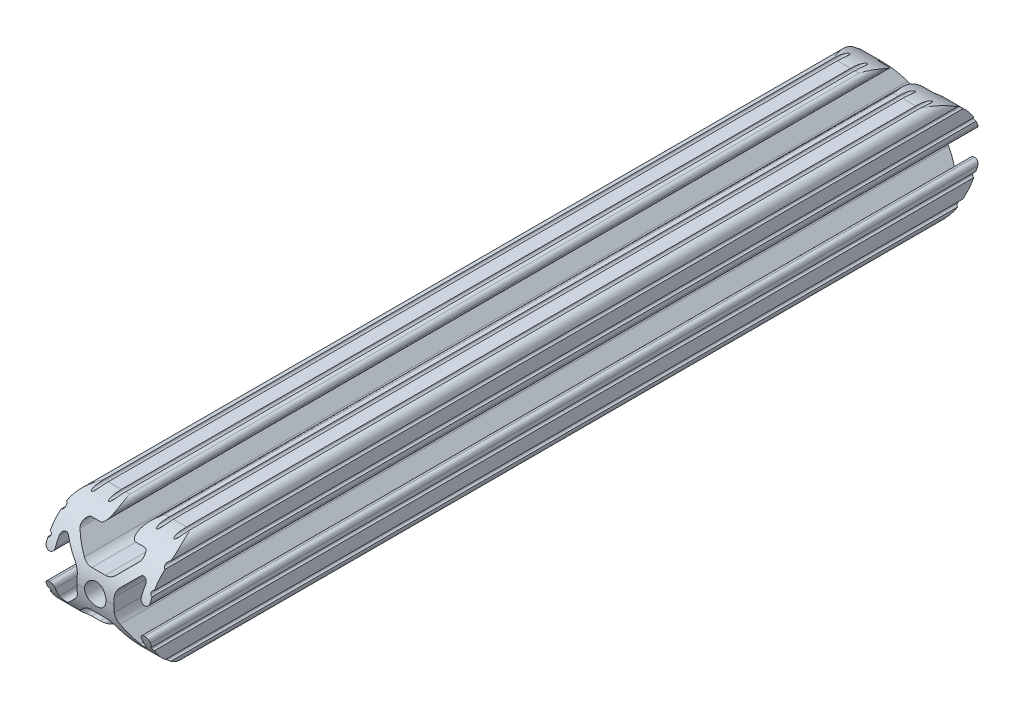
SolidWorks part; units mm, degrees
material "6061 Alloy"
ref_plane "Front Plane" through (0, 0, 0) normal (0, 0, 1) x (1, 0, 0)
ref_plane "Top Plane" through (0, 0, 0) normal (0, 1, 0) x (1, 0, 0)
ref_plane "Right Plane" through (0, 0, 0) normal (1, 0, 0) x (0, 0, -1)
sketch "Sketch1" plane through (0, 0, 0) normal (0, 0, 1) x (1, 0, 0)
  line L88 (-7.1797, -8.6452) -> (-3.9523, -5.4237)
  line L89 (-1.7093, -4.4958) -> (1.7093, -4.4958)
  line L90 (3.9523, -5.4237) -> (7.1797, -8.6452)
  line L91 (6.4164, -10.4902) -> (4.2875, -10.4902)
  line L92 (3.2385, -11.5392) -> (3.2385, -11.651)
  line L93 (4.2875, -12.7) -> (5.3171, -12.7)
  line L94 (6.3331, -12.7) -> (9.5504, -12.7)
  line L95 (12.7, -9.5504) -> (12.7, -6.3331)
  line L96 (12.7, -5.3171) -> (12.7, -4.2875)
  line L97 (11.651, -3.2385) -> (11.5392, -3.2385)
  line L98 (10.4902, -4.2875) -> (10.4902, -6.4021)
  line L99 (8.7371, -7.1294) -> (5.441, -3.8408)
  line L100 (4.5085, -1.5932) -> (4.5085, 1.5932)
  line L101 (5.441, 3.8408) -> (8.7371, 7.1294)
  line L102 (10.4902, 6.4021) -> (10.4902, 4.2875)
  line L103 (11.5392, 3.2385) -> (11.651, 3.2385)
  line L104 (12.7, 4.2875) -> (12.7, 5.3171)
  line L105 (12.7, 6.3331) -> (12.7, 9.5504)
  line L106 (9.5504, 12.7) -> (6.3331, 12.7)
  line L107 (5.3171, 12.7) -> (4.2875, 12.7)
  line L108 (3.2385, 11.651) -> (3.2385, 11.5392)
  line L109 (4.2875, 10.4902) -> (6.4768, 10.4902)
  line L110 (7.207, 8.7244) -> (3.8983, 5.4232)
  line L111 (1.6558, 4.4958) -> (-1.6558, 4.4958)
  line L112 (-3.8983, 5.4232) -> (-7.207, 8.7244)
  line L113 (-6.4768, 10.4902) -> (-4.2875, 10.4902)
  line L114 (-3.2385, 11.5392) -> (-3.2385, 11.651)
  line L115 (-4.2875, 12.7) -> (-5.3171, 12.7)
  line L116 (-6.3331, 12.7) -> (-9.5504, 12.7)
  line L117 (-12.7, 9.5504) -> (-12.7, 6.3331)
  line L118 (-12.7, 5.3171) -> (-12.7, 4.2875)
  line L119 (-11.651, 3.2385) -> (-11.5392, 3.2385)
  line L120 (-10.4902, 4.2875) -> (-10.4902, 6.4021)
  line L121 (-8.7371, 7.1294) -> (-5.441, 3.8408)
  line L122 (-4.5085, 1.5932) -> (-4.5085, -1.5932)
  line L123 (-5.441, -3.8408) -> (-8.7371, -7.1294)
  line L124 (-10.4902, -6.4021) -> (-10.4902, -4.2875)
  line L125 (-11.5392, -3.2385) -> (-11.651, -3.2385)
  line L126 (-12.7, -4.2875) -> (-12.7, -5.3171)
  line L127 (-12.7, -6.3331) -> (-12.7, -9.5504)
  line L128 (-9.5504, -12.7) -> (-6.3331, -12.7)
  line L129 (-5.3171, -12.7) -> (-4.2875, -12.7)
  line L130 (-3.2385, -11.651) -> (-3.2385, -11.5392)
  line L131 (-4.2875, -10.4902) -> (-6.4164, -10.4902)
  circle A1 centre (0, 0) radius 2.6035
  arc A104 (-7.1797, -8.6452) -> (-6.4164, -10.4902) centre (-6.4164, -9.4098) ccw
  arc A105 (-1.7093, -4.4958) -> (-3.9523, -5.4237) centre (-1.7093, -7.6708) ccw
  arc A106 (3.9523, -5.4237) -> (1.7093, -4.4958) centre (1.7093, -7.6708) ccw
  arc A107 (6.4164, -10.4902) -> (7.1797, -8.6452) centre (6.4164, -9.4098) ccw
  arc A108 (4.2875, -10.4902) -> (3.2385, -11.5392) centre (4.2875, -11.5392) ccw
  arc A109 (3.2385, -11.651) -> (4.2875, -12.7) centre (4.2875, -11.651) ccw
  arc A110 (6.3331, -12.7) -> (5.3171, -12.7) centre (5.8251, -12.7) ccw
  arc A111 (10.5664, -12.6998) -> (9.5504, -12.7) centre (10.0584, -12.7) ccw
  arc A112 (10.5664, -12.6998) -> (12.6998, -10.5664) centre (10.5918, -10.5918) ccw
  arc A113 (12.7, -9.5504) -> (12.6998, -10.5664) centre (12.7, -10.0584) ccw
  arc A114 (12.7, -5.3171) -> (12.7, -6.3331) centre (12.7, -5.8251) ccw
  arc A115 (12.7, -4.2875) -> (11.651, -3.2385) centre (11.651, -4.2875) ccw
  arc A116 (11.5392, -3.2385) -> (10.4902, -4.2875) centre (11.5392, -4.2875) ccw
  arc A117 (8.7371, -7.1294) -> (10.4902, -6.4021) centre (9.4628, -6.4021) ccw
  arc A118 (4.5085, -1.5932) -> (5.441, -3.8408) centre (7.6835, -1.5932) ccw
  arc A119 (5.441, 3.8408) -> (4.5085, 1.5932) centre (7.6835, 1.5932) ccw
  arc A120 (10.4902, 6.4021) -> (8.7371, 7.1294) centre (9.4628, 6.4021) ccw
  arc A121 (10.4902, 4.2875) -> (11.5392, 3.2385) centre (11.5392, 4.2875) ccw
  arc A122 (11.651, 3.2385) -> (12.7, 4.2875) centre (11.651, 4.2875) ccw
  arc A123 (12.7, 6.3331) -> (12.7, 5.3171) centre (12.7, 5.8251) ccw
  arc A124 (12.6998, 10.5664) -> (12.7, 9.5504) centre (12.7, 10.0584) ccw
  arc A125 (12.6998, 10.5664) -> (10.5664, 12.6998) centre (10.5918, 10.5918) ccw
  arc A126 (9.5504, 12.7) -> (10.5664, 12.6998) centre (10.0584, 12.7) ccw
  arc A127 (5.3171, 12.7) -> (6.3331, 12.7) centre (5.8251, 12.7) ccw
  arc A128 (4.2875, 12.7) -> (3.2385, 11.651) centre (4.2875, 11.651) ccw
  arc A129 (3.2385, 11.5392) -> (4.2875, 10.4902) centre (4.2875, 11.5392) ccw
  arc A130 (7.207, 8.7244) -> (6.4768, 10.4902) centre (6.4768, 9.4563) ccw
  arc A131 (1.6558, 4.4958) -> (3.8983, 5.4232) centre (1.6558, 7.6708) ccw
  arc A132 (-3.8983, 5.4232) -> (-1.6558, 4.4958) centre (-1.6558, 7.6708) ccw
  arc A133 (-6.4768, 10.4902) -> (-7.207, 8.7244) centre (-6.4768, 9.4563) ccw
  arc A134 (-4.2875, 10.4902) -> (-3.2385, 11.5392) centre (-4.2875, 11.5392) ccw
  arc A135 (-3.2385, 11.651) -> (-4.2875, 12.7) centre (-4.2875, 11.651) ccw
  arc A136 (-6.3331, 12.7) -> (-5.3171, 12.7) centre (-5.8251, 12.7) ccw
  arc A137 (-10.5664, 12.6998) -> (-9.5504, 12.7) centre (-10.0584, 12.7) ccw
  arc A138 (-10.5664, 12.6998) -> (-12.6998, 10.5664) centre (-10.5918, 10.5918) ccw
  arc A139 (-12.7, 9.5504) -> (-12.6998, 10.5664) centre (-12.7, 10.0584) ccw
  arc A140 (-12.7, 5.3171) -> (-12.7, 6.3331) centre (-12.7, 5.8251) ccw
  arc A141 (-12.7, 4.2875) -> (-11.651, 3.2385) centre (-11.651, 4.2875) ccw
  arc A142 (-11.5392, 3.2385) -> (-10.4902, 4.2875) centre (-11.5392, 4.2875) ccw
  arc A143 (-8.7371, 7.1294) -> (-10.4902, 6.4021) centre (-9.4628, 6.4021) ccw
  arc A144 (-4.5085, 1.5932) -> (-5.441, 3.8408) centre (-7.6835, 1.5932) ccw
  arc A145 (-5.441, -3.8408) -> (-4.5085, -1.5932) centre (-7.6835, -1.5932) ccw
  arc A146 (-10.4902, -6.4021) -> (-8.7371, -7.1294) centre (-9.4628, -6.4021) ccw
  arc A147 (-10.4902, -4.2875) -> (-11.5392, -3.2385) centre (-11.5392, -4.2875) ccw
  arc A148 (-11.651, -3.2385) -> (-12.7, -4.2875) centre (-11.651, -4.2875) ccw
  arc A149 (-12.7, -6.3331) -> (-12.7, -5.3171) centre (-12.7, -5.8251) ccw
  arc A150 (-12.6998, -10.5664) -> (-12.7, -9.5504) centre (-12.7, -10.0584) ccw
  arc A151 (-12.6998, -10.5664) -> (-10.5664, -12.6998) centre (-10.5918, -10.5918) ccw
  arc A152 (-9.5504, -12.7) -> (-10.5664, -12.6998) centre (-10.0584, -12.7) ccw
  arc A153 (-5.3171, -12.7) -> (-6.3331, -12.7) centre (-5.8251, -12.7) ccw
  arc A154 (-4.2875, -12.7) -> (-3.2385, -11.651) centre (-4.2875, -11.651) ccw
  arc A155 (-3.2385, -11.5392) -> (-4.2875, -10.4902) centre (-4.2875, -11.5392) ccw
extrude "Boss-Extrude1" add sketch "Sketch1" along normal mid plane 203.2
sketch "Sketch2" plane through (12.7, 0, 0) normal (1, 0, 0) x (0, 0, -1)
  line L0 (-101.6, 0) -> (101.6, 0) construction
  line L1 (-101.6, -1.5932) -> (-101.6, 1.5932) construction
  line L2 (101.6, -1.5932) -> (101.6, 1.5932) construction
  circle A0 centre (-88.9, 0) radius 3.175
  circle A1 centre (-63.5, 0) radius 3.175
  dimension "D1" = 12.7
  dimension "D3" = 6.35
  dimension "D2" = 25.4
fillet "Fillet1" radius 12.7 4 edges at (7.9418, -12.7, -101.6) (7.9418, 12.7, -101.6) (7.9418, -12.7, 101.6) (7.9418, 12.7, 101.6)
extrude "Cut-Extrude1" cut sketch "Sketch2" against normal through all
